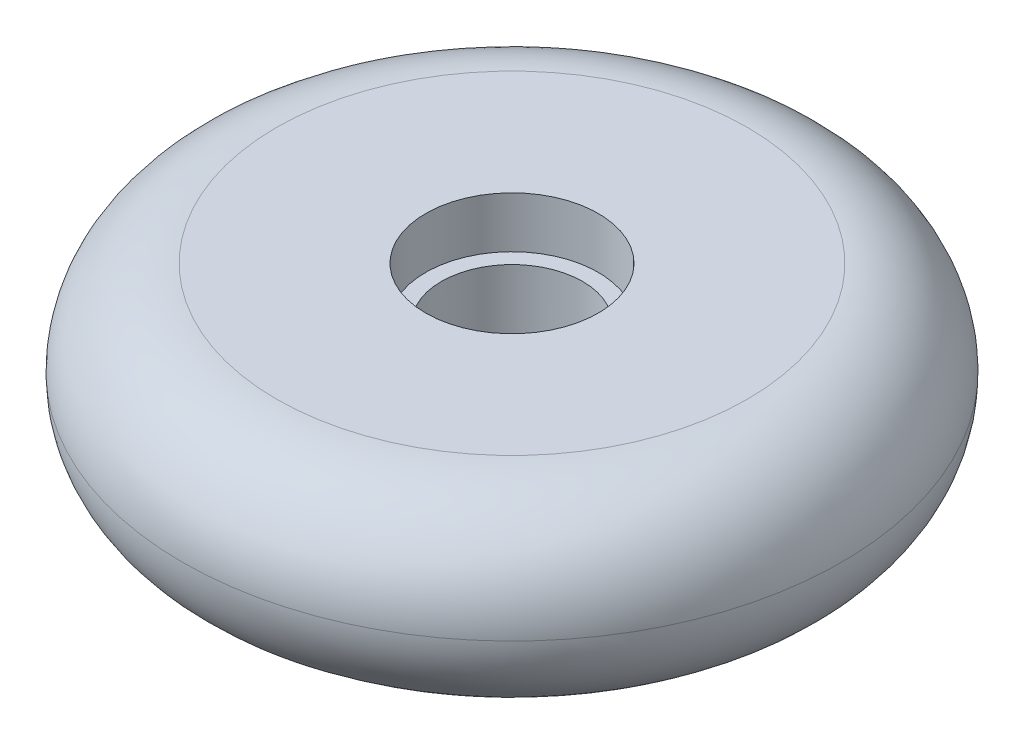
SolidWorks part; units mm, degrees
ref_plane "Front Plane" through (0, 0, 0) normal (0, 0, 1) x (1, 0, 0)
ref_plane "Top Plane" through (0, 0, 0) normal (0, 1, 0) x (1, 0, 0)
ref_plane "Right Plane" through (0, 0, 0) normal (1, 0, 0) x (0, 0, -1)
sketch "Sketch1" plane through (0, 0, 0) normal (0, 1, 0) x (1, 0, 0)
  circle A0 centre (0, 0) radius 42
  dimension "D1" = 84
extrude "Boss-Extrude1" add sketch "Sketch1" along normal blind 24
fillet "Fillet1" radius 12 2 edges at (0, 0, 42) (0, 24, 42)
sketch "Sketch2" plane through (0, 24, 0) normal (0, 1, 0) x (1, 0, 0)
  circle A0 centre (0, 0) radius 11
  dimension "D1" = 22
extrude "Cut-Extrude1" cut sketch "Sketch2" against normal blind 6.5
sketch "Sketch3" plane through (0, 0, 0) normal (0, -1, 0) x (1, 0, 0)
  circle A0 centre (0, 0) radius 11
  dimension "D1" = 22
extrude "Cut-Extrude2" cut sketch "Sketch3" against normal blind 6.5
sketch "Sketch4" plane through (0, 6.5, 0) normal (0, -1, 0) x (1, 0, 0)
  circle A0 centre (0, 0) radius 9
  dimension "D1" = 18
extrude "Cut-Extrude3" cut sketch "Sketch4" against normal through all
